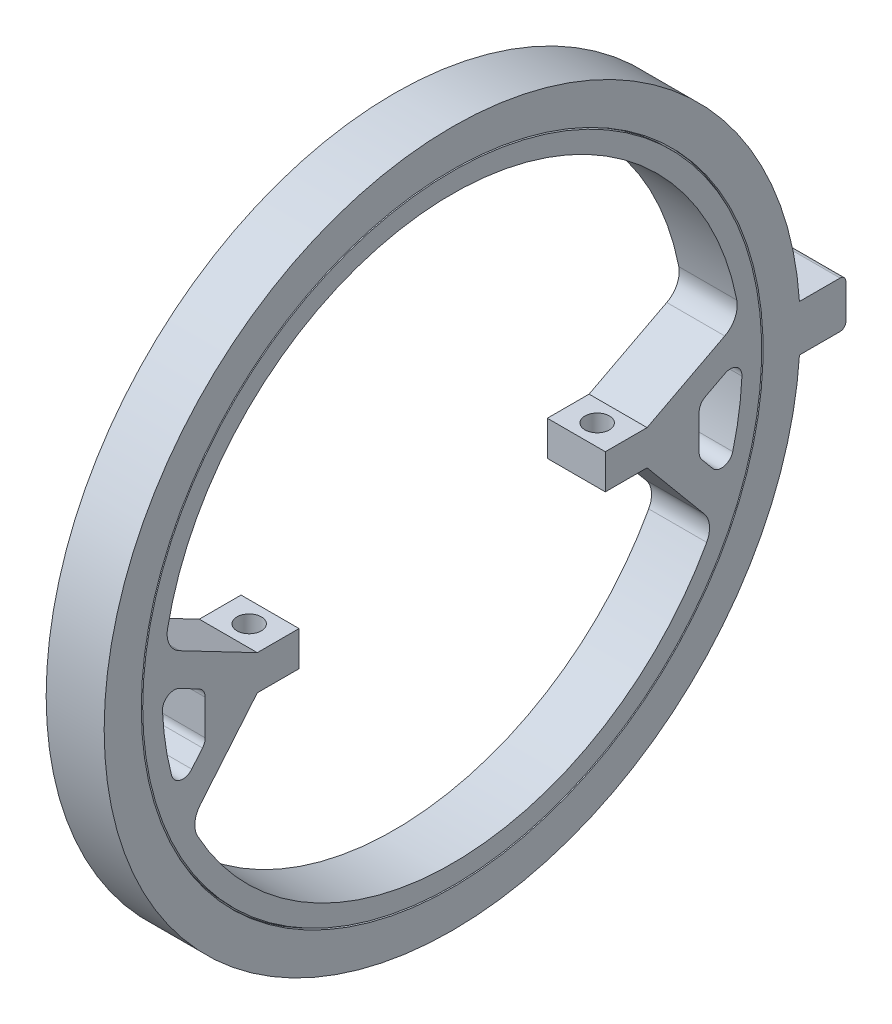
SolidWorks part; units mm, degrees
note: The reader was unsure of these and kept them because the rebuilt part matched: shared geometry of "Sketch2<3>".
ref_plane "Front Plane" through (0, 0, 0) normal (0, 0, 1) x (1, 0, 0)
ref_plane "Top Plane" through (0, 0, 0) normal (0, 1, 0) x (1, 0, 0)
ref_plane "Right Plane" through (0, 0, 0) normal (1, 0, 0) x (0, 0, -1)
sketch "Sketch2" plane through (0, 0, 0) normal (0, 1, 0) x (1, 0, 0)
  line L0 (0, 30) -> (-2.5, 30)
  line L1 (-2.5, 30) -> (-2.5, 26.8)
  line L2 (-2.5, 26.8) -> (-2.2315, 26.8)
  line L3 (-2.2315, 26.8) -> (-1.25, 28.5)
  line L4 (-1.25, 28.5) -> (0, 28.5)
  line L5 (0, 28.5) -> (0, 30)
  line L6 (0, 0) -> (0, 45848.0641) construction
  line L7 (0, 0) -> (50000, 0) construction
  line L8 (0, 28.38) -> (-1.1807, 28.38)
  line L9 (-1.1807, 28.38) -> (-2.1622, 26.68)
  line L10 (-2.1622, 26.68) -> (-2.5, 26.68)
  line L11 (-2.5, 26.68) -> (-2.5, 25)
  line L12 (-2.5, 25) -> (0, 25)
  line L13 (0, 25) -> (0, 28.38)
  line L14 (-1.1807, 28.38) -> (-1.1807, 28.5) construction
  line L15 (-2.5, 26.8) -> (-2.5, 26.68) construction
  line L16 (-2.2315, 26.8) -> (-2.1276, 26.74)
  dimension "D1" = 30
  dimension "D2" = 0.12
  dimension "D3" = 1.5
  dimension "D4" = 5
  dimension "D5" = 25
  dimension "D6" = 60
  dimension "D7" = 1.7
  dimension "D8" = 2.5
  dimension "D9" = 0.12
revolve "Revolve1" add sketch "Sketch2" angle 360 about L7
revolve "Revolve2" add sketch "Sketch2<3>" angle 180 mid plane about L7
sketch "Sketch2<3>" plane through (0, 0, 0) normal (0, 1, 0) x (1, 0, 0) same geometry as "Sketch2"
mirror "Mirror1" about plane through (0, 0, 0) normal (1, 0, 0) of "Revolve2", "Revolve1"
sketch "Sketch3" plane through (0, 0, 0) normal (1, 0, 0) x (0, 0, -1)
  line L0 (16.8, -0.85) -> (13.2, -0.85)
  line L1 (13.2, -0.85) -> (13.2, -3.85)
  line L2 (13.2, -3.85) -> (16.8, -3.85)
  line L3 (0, 0) -> (50000, 0) construction
  line L4 (0, 0) -> (0, 50000) construction
  line L5 (16.8, -0.85) -> (24.7796, 3.3125)
  line L6 (16.8, -3.85) -> (22.5656, -10.7607)
  line L7 (24.9927, 0.604) -> (21.289, -1.3281)
  line L8 (21.289, -1.3281) -> (21.289, -5.3281)
  line L9 (21.289, -5.3281) -> (23.6369, -8.1423)
  line L10 (21.289, -1.3281) -> (20.1327, 0.8885) construction
  line L11 (21.289, -5.3281) -> (19.3693, -6.9296) construction
  arc A0 (0, -25) -> (0, 25) centre (0, 0) ccw construction
  arc A1 (0, -25) -> (0, 25) centre (0, 0) ccw
  dimension "D1" = 0.85
  dimension "D2" = 3
  dimension "D3" = 26.4
  dimension "D4" = 9
  dimension "D5" = 2.5
  dimension "D6" = 4
  dimension "D7" = 3.6
extrude "Boss-Extrude1" add sketch "Sketch3" along normal mid plane 5 contours L7 A1 L5 L0 L1 L2 L6 L9 L8
fillet "Fillet1" radius 2 2 edges at (0, -10.7607, -22.5656) (0, 3.3125, -24.7796)
fillet "Fillet2" radius 1 4 edges at (0, -1.3281, -21.289) (0, -5.3281, -21.289) (0, 0.604, -24.9927) (0, -8.1423, -23.6369)
sketch "Sketch4" plane through (0, 0, 0) normal (0, 1, 0) x (1, 0, 0)
  circle A0 centre (0, 15) radius 1.05
  dimension "D1" = 15
  dimension "D2" = 2.1
extrude "Cut-Extrude1" cut sketch "Sketch4" against normal up to next
mirror "Mirror2" about plane through (0, 0, 0) normal (0, 0, 1) of bodies 107
sketch "Sketch5" plane through (0, 0, 0) normal (1, 0, 0) x (0, 0, -1)
  line L0 (29.9333, 2) -> (29.9333, -2)
  line L1 (29.9333, -2) -> (33.9333, -2)
  line L2 (33.9333, -2) -> (33.9333, 2)
  line L3 (33.9333, 2) -> (29.9333, 2)
  circle A0 centre (0, 0) radius 30 construction
  dimension "D1" = 4
  dimension "D2" = 4
extrude "Boss-Extrude2" add sketch "Sketch5" along normal mid plane 5
fillet "Fillet3" radius 0.5 2 edges at (0, -2, -33.9333) (0, 2, -33.9333)
